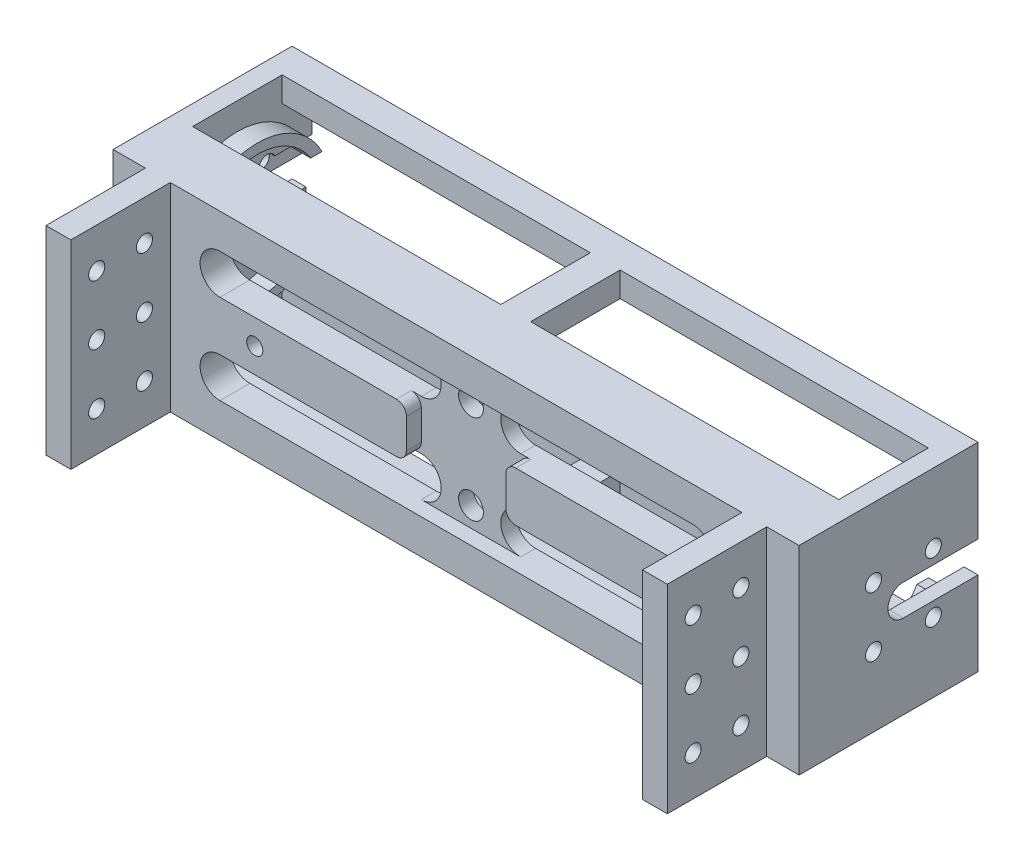
SolidWorks part; units mm, degrees
ref_plane "Plano frontal" through (0, 0, 0) normal (0, 0, 1) x (1, 0, 0)
ref_plane "Plano superior" through (0, 0, 0) normal (0, 1, 0) x (1, 0, 0)
ref_plane "Plano direito" through (0, 0, 0) normal (1, 0, 0) x (0, 0, -1)
sketch "Esboço1" plane through (0, 0, 0) normal (0, 0, 1) x (1, 0, 0)
  line L1 (32.5, -20) -> (-32.5, -20)
  line L2 (32.5, -20) -> (32.5, 20)
  line L3 (32.5, 20) -> (-32.5, 20)
  line L4 (-32.5, -20) -> (-32.5, 20)
  line L5 (32.5, -20) -> (-32.5, 20) construction
  line L6 (32.5, 20) -> (-32.5, -20) construction
  point P0 (0, 0)
  dimension "D1" = 65
  dimension "D2" = 40
extrude "Ressalto-extrusão1" add sketch "Esboço1" along normal blind 6
sketch "Esboço2" plane through (-32.5, 0, 0) normal (-1, 0, 0) x (0, 0, 1)
  line L0 (0, 20) -> (-30, 20)
  line L1 (-30, 20) -> (-30, -20)
  line L2 (-30, -20) -> (0, -20)
  line L4 (0, 20) -> (0, -20)
  line L5 (0, -20) -> (6, -20)
  line L6 (6, -20) -> (6, 20)
  line L7 (6, 20) -> (0, 20)
  line L8 (0, 20) -> (0, -20) construction
  line L9 (0, -20) -> (6, -20)
  line L10 (6, -20) -> (6, 20)
  line L11 (6, 20) -> (0, 20)
  dimension "D2" = 30
  dimension "D1" = 0
extrude "Ressalto-extrusão2" add sketch "Esboço2" along normal blind 4
sketch "Esboço3" plane through (-36.5, 0, 0) normal (-1, 0, 0) x (0, 0, 1)
  line L0 (0, 20) -> (0, -20) construction
  line L1 (0, 20) -> (0, -20) construction
  line L2 (-15, 3.125) -> (-30, 3.125)
  line L3 (0, 20) -> (-30, 20) construction
  line L4 (0, 20) -> (0, -20) construction
  line L5 (0, -20) -> (-30, -20) construction
  line L6 (-30, 20) -> (-30, -20) construction
  line L7 (-15, -20) -> (-15, 20) construction
  line L8 (0, 0) -> (-30, 0) construction
  line L9 (-30, 3.125) -> (-30, -3.125)
  line L10 (-30, -3.125) -> (-15, -3.125)
  arc A0 (-15, -3.125) -> (-15, 3.125) centre (-15, 0) ccw
  point P276 (-15, 0)
  dimension "D1" = 6.25
extrude "Corte-extrusão1" cut sketch "Esboço3" against normal through all
sketch "Esboço5" plane through (0, 0, 6) normal (0, 0, 1) x (1, 0, 0)
  line L0 (-36.5, -20) -> (32.5, -20) construction
  line L1 (-36.5, 20) -> (-30, 20)
  line L2 (-36.5, 20) -> (-36.5, -20)
  line L3 (-36.5, -20) -> (-30, -20)
  line L4 (-30, 20) -> (-30, -20)
  line L6 (-30, 20) -> (-25, 20)
  line L7 (-30, 20) -> (-30, -20)
  line L8 (-30, -20) -> (-25, -20)
  line L9 (-25, 20) -> (-25, -20)
  line L10 (-25, 20) -> (-21.5, 20)
  line L11 (-25, 20) -> (-25, -20)
  line L12 (-25, -20) -> (-21.5, -20)
  line L13 (-21.5, 20) -> (-21.5, -20)
  line M5 (32.5, 20) -> (-36.5, 20)
  line M7 (-36.5, -20) -> (32.5, -20)
  dimension "D1" = 15
  dimension "D2" = 6.5
  dimension "D3" = 5
extrude "Ressalto-extrusão4" add sketch "Esboço5" along normal blind 20 contours L9 L4 M5 M7 region at (-27.5, 0, 6)
sketch "Esboço7" plane through (-32.5, 0, 0) normal (1, 0, 0) x (0, 0, -1)
  line L0 (15, -6.625) -> (30, -6.625)
  line L1 (30, -3.125) -> (30, -20) construction
  line L2 (30, -6.625) -> (30, 6.625)
  line L3 (30, 20) -> (30, 3.125) construction
  line L4 (30, 6.625) -> (15, 6.625)
  arc A0 (15, 6.625) -> (15, -6.625) centre (15, 0) ccw
  dimension "D1" = 13.25
extrude "Corte-extrusão3" cut sketch "Esboço7" against normal blind 1.2
sketch "Esboço8" plane through (-32.5, 0, 0) normal (1, 0, 0) x (0, 0, -1)
  line L4 (15, -6.625) -> (30, -6.625) construction
  line L5 (25.7471, -6.625) -> (28.0384, -6.625)
  line L6 (30, 6.625) -> (15, 6.625) construction
  line L7 (28.0384, 6.625) -> (25.7471, 6.625)
  arc A0 (25.7471, 6.625) -> (25.7471, -6.625) centre (15, 0) ccw
  arc A1 (28.0384, 6.625) -> (28.0384, -6.625) centre (15, 0) ccw
  dimension "D1" = 25.25
extrude "Ressalto-extrusão5" add sketch "Esboço8" along normal blind 4
sketch "Esboço11" plane through (0, 0, 6) normal (0, 0, 1) x (1, 0, 0)
  line L0 (-15, 9) -> (22.5, 9) construction
  line L1 (-15, 13) -> (22.5, 13)
  line L2 (-15, 5) -> (22.5, 5)
  line L3 (-15, -9) -> (22.5, -9) construction
  line L4 (-15, -5) -> (22.5, -5)
  line L5 (-15, -13) -> (22.5, -13)
  line L6 (32.5, -20) -> (32.5, 20) construction
  line L7 (-25, 20) -> (-25, -20) construction
  line L8 (32.5, 20) -> (-25, 20) construction
  line L9 (-25, -20) -> (32.5, -20) construction
  line L10 (3.75, 20) -> (3.75, -20) construction
  arc A0 (-15, 13) -> (-15, 5) centre (-15, 9) ccw
  arc A1 (22.5, 5) -> (22.5, 13) centre (22.5, 9) ccw
  arc A2 (-15, -5) -> (-15, -13) centre (-15, -9) ccw
  arc A3 (22.5, -13) -> (22.5, -5) centre (22.5, -9) ccw
  point P2 (3.75, 9)
  point P7 (3.75, -9)
  dimension "D1" = 10
  dimension "D2" = 10
  dimension "D3" = 7
  dimension "D4" = 7
  dimension "D5" = 10
extrude "Corte-extrusão4" cut sketch "Esboço11" against normal through all
sketch "Esboço12" plane through (-32.5, 0, 0) normal (1, 0, 0) x (0, 0, -1)
  line L14 (0, -20) -> (6, -20)
  line L15 (0, -20) -> (0, -15)
  line L16 (0, -15) -> (6, -15)
  line L17 (6, -20) -> (6, -15)
  line L18 (30, -20) -> (24, -20)
  line L19 (30, -20) -> (30, -15)
  line L20 (30, -15) -> (24, -15)
  line L21 (24, -20) -> (24, -15)
  dimension "D1" = 5
  dimension "D3" = 6
extrude "Ressalto-extrusão6" add sketch "Esboço12" along normal up to surface (65 mm away) up to face at (32.5, 0, 3)
sketch "Esboço13" plane through (0, 0, -24) normal (0, 0, 1) x (1, 0, 0)
  line L0 (32.5, -15) -> (-32.5, -15) construction
  line L1 (32.5, -20) -> (29.5, -20)
  line L2 (32.5, -20) -> (32.5, -15)
  line L3 (32.5, -15) -> (29.5, -15)
  line L4 (29.5, -20) -> (29.5, -15)
  dimension "D1" = 3
extrude "Ressalto-extrusão7" add sketch "Esboço13" along normal up to surface (18 mm away) up to face at (0, -17.5, -6)
ref_plane "Plano1" through (0, 0, 0) normal (0, 1, 0) x (1, 0, 0)
mirror "Espelhar2" about plane through (0, 0, 0) normal (0, 1, 0) of "Ressalto-extrusão6", "Ressalto-extrusão7"
sketch "Esboço15" plane through (-30, 0, 0) normal (-1, 0, 0) x (0, 0, 1)
  line L0 (6, 0) -> (26, 0) construction
  line L1 (6, 20) -> (6, -20) construction
  line L2 (26, 20) -> (26, -20) construction
  line L3 (20.8, 20) -> (20.8, -20) construction
  line L4 (26, -20) -> (6, -20) construction
  line L5 (26, 20) -> (6, 20) construction
  line L6 (11.2, 20) -> (11.2, -20) construction
  line L7 (20.8, -12) -> (11.2, -12) construction
  line L8 (20.8, 12) -> (11.2, 12) construction
  circle A0 centre (20.8, 12) radius 1.625
  circle A1 centre (11.2, 12) radius 1.625
  circle A2 centre (20.8, 0) radius 1.625
  circle A3 centre (11.2, 0) radius 1.625
  circle A4 centre (20.8, -12) radius 1.625
  circle A5 centre (11.2, -12) radius 1.625
  dimension "D5" = 3.25
  dimension "D1" = 5.2
  dimension "D2" = 5.2
  dimension "D3" = 8
  dimension "D4" = 8
extrude "Corte-extrusão5" cut sketch "Esboço15" against normal up to surface (5 mm away) up to face at (-25, 0, 16)
ref_plane "Plano2" through (32.5, 0, 0) normal (1, 0, 0) x (0, 0, -1)
sketch "Esboço18" plane through (0, 0, 6) normal (0, 0, 1) x (1, 0, 0)
  line L0 (32.5, -20) -> (32.5, 20) construction
  line L1 (32.5, -20) -> (32.5, 20)
  line L2 (32.5, 0) -> (-25, 0) construction
  line L3 (-25, 20) -> (-25, -20) construction
  line L4 (-25, 20) -> (-25, -20)
  circle A0 centre (-8, 0) radius 1.625
  dimension "D2" = 3.25
  dimension "D1" = 40.5
extrude "Corte-extrusão6" cut sketch "Esboço18" against normal up to surface (6 mm away) contours A0 L2 | L2 A0 region at (-8, -0.6897, 6) region at (-8, 0.6897, 6) up to face at (3.75, -9, 0)
sketch "Esboço19" plane through (0, 0, 0) normal (0, 0, -1) x (-1, 0, 0)
  circle A0 centre (8, 0) radius 2.875
  dimension "D1" = 5.75
extrude "Corte-extrusão7" cut sketch "Esboço19" against normal blind 1.5
sketch "Esboço22" plane through (-36.5, 0, 0) normal (-1, 0, 0) x (0, 0, 1)
  line L0 (-8.9896, 6.0104) -> (-15, 0) construction
  line L1 (-15, 0) -> (-8.9896, 0) construction
  line L2 (-8.9896, 0) -> (-8.9896, 6.0104) construction
  circle A0 centre (-8.9896, 6.0104) radius 1.625
  circle A1 centre (-21.0104, 6.0104) radius 1.625
  circle A2 centre (-21.0104, -6.0104) radius 1.625
  circle A3 centre (-8.9896, -6.0104) radius 1.625
  point P15 (-15, 0)
  dimension "D3" = 3.25
  dimension "D1" = 8.5
  dimension "D2" = 45
  dimension "D4" = 4
extrude "Corte-extrusão10" cut sketch "Esboço22" against normal blind 4
mirror "Espelhar3" about plane through (32.5, 0, 0) normal (1, 0, 0) of bodies 121 115
sketch "Esboço20" plane through (0, 0, 6) normal (0, 0, 1) x (1, 0, 0)
  line L0 (42.5, -13) -> (22.5, -13)
  line L1 (22.5, -13) -> (22.5, -5)
  line L3 (42.5, -5) -> (42.5, -13)
  line L4 (42.5, 5) -> (42.5, 13)
  line L5 (42.5, 13) -> (22.5, 13)
  line L6 (22.5, 13) -> (22.5, 5)
  line L8 (42.5, 5) -> (42.5, -5)
  line L9 (22.5, -5) -> (22.5, 5)
  arc A0 (22.5, 5) -> (22.5, 13) centre (22.5, 9) ccw construction
extrude "Corte-extrusão8" cut sketch "Esboço20" against normal blind 3
sketch "Esboço21" plane through (0, 0, 3) normal (0, 0, 1) x (1, 0, 0)
  line L0 (26.5, 9) -> (38.5, 9) construction
  line L1 (26.5, -9) -> (38.5, -9) construction
  arc A0 (22.5, 5) -> (22.5, 13) centre (22.5, 9) ccw construction
  arc A1 (42.5, 13) -> (42.5, 5) centre (42.5, 9) ccw construction
  arc A2 (22.5, -13) -> (22.5, -5) centre (22.5, -9) ccw construction
  arc A3 (42.5, -5) -> (42.5, -13) centre (42.5, -9) ccw construction
  circle A4 centre (32.5, 9) radius 2.5
  circle A5 centre (32.5, -9) radius 2.5
  dimension "D1" = 5
extrude "Corte-extrusão9" cut sketch "Esboço21" against normal up to surface (3 mm away) up to face at (-10.875, 0, 0)
fillet "Filete1" radius 2 4 edges at (22.5, -5, 4.5) (22.5, 5, 4.5) (42.5, 5, 4.5) (42.5, -5, 4.5)
equation "\"3d\"= 0.25mm"
equation "\"D5@Esboço15\"= 3.00mm +\"3d\""
equation "\"D3@Esboço22\"=3.00mm +\"3d\""
equation "\"D2@Esboço18\"= 3.00mm +\"3d\""
equation "\"D1@Esboço3\"= 6.0mm + \"3d\""
equation "\"D1@Esboço7\"=13.00mm + \"3d\""
equation "\"D1@Esboço8\"= 25mm + \"3d\""
equation "\"D1@Esboço19\"= 5.5mm + \"3d\""
